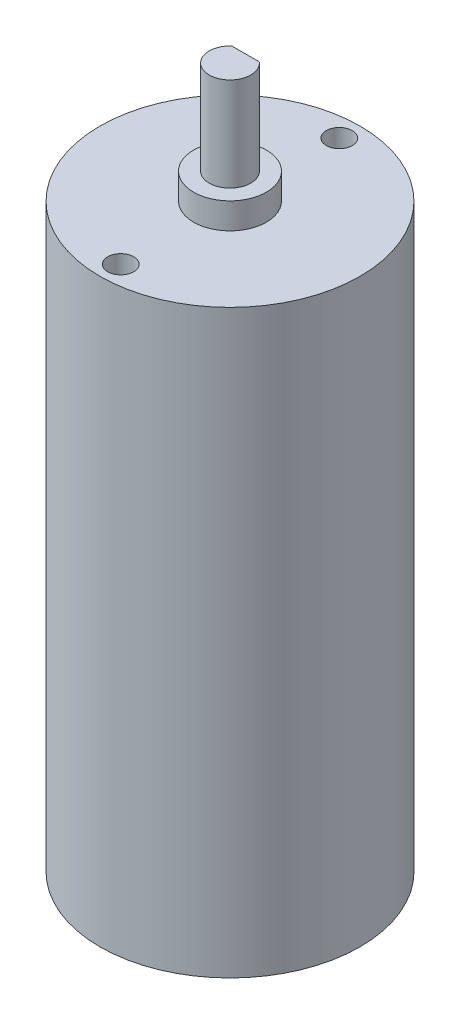
SolidWorks part; units mm, degrees
ref_plane "Front Plane" through (0, 0, 0) normal (0, 0, 1) x (1, 0, 0)
ref_plane "Top Plane" through (0, 0, 0) normal (0, 1, 0) x (1, 0, 0)
ref_plane "Right Plane" through (0, 0, 0) normal (1, 0, 0) x (0, 0, -1)
sketch "Sketch1" plane through (0, 0, 0) normal (0, 1, 0) x (1, 0, 0)
  circle A0 centre (0, 0) radius 12.5
  dimension "D1" = 25
extrude "Boss-Extrude1" add sketch "Sketch1" along normal blind 55.8
sketch "Sketch2" plane through (0, 55.8, 0) normal (0, 1, 0) x (1, 0, 0)
  circle A0 centre (0, 0) radius 3.5
  circle A1 centre (0, 10.5) radius 1.25
  circle A2 centre (0, -10.5) radius 1.25
  dimension "D1" = 7
  dimension "D2" = 2.5
  dimension "D3" = 21
  dimension "D4" = 10.5
extrude "Cut-Extrude1" cut sketch "Sketch2" against normal blind 5 contours A1 | A2 region at (0, 55.8, -10.5)
extrude "Boss-Extrude2" add sketch "Sketch2<3>" along normal blind 2.5 contours A0 region at (0, 55.8, 0)
sketch "Sketch2<3>" plane through (0, 55.8, 0) normal (0, 1, 0) x (1, 0, 0) same geometry as "Sketch2"
sketch "Sketch3" plane through (0, 58.3, 0) normal (0, 1, 0) x (1, 0, 0)
  line L0 (-1.3229, 1.5) -> (1.3229, 1.5)
  circle A0 centre (0, 0) radius 2
  point P5 (0, -2)
  dimension "D1" = 4
  dimension "D2" = 3.5
extrude "Boss-Extrude3" add sketch "Sketch3" along normal blind 9 contours L0 A0 region at (0, 58.3, 0.1324)
